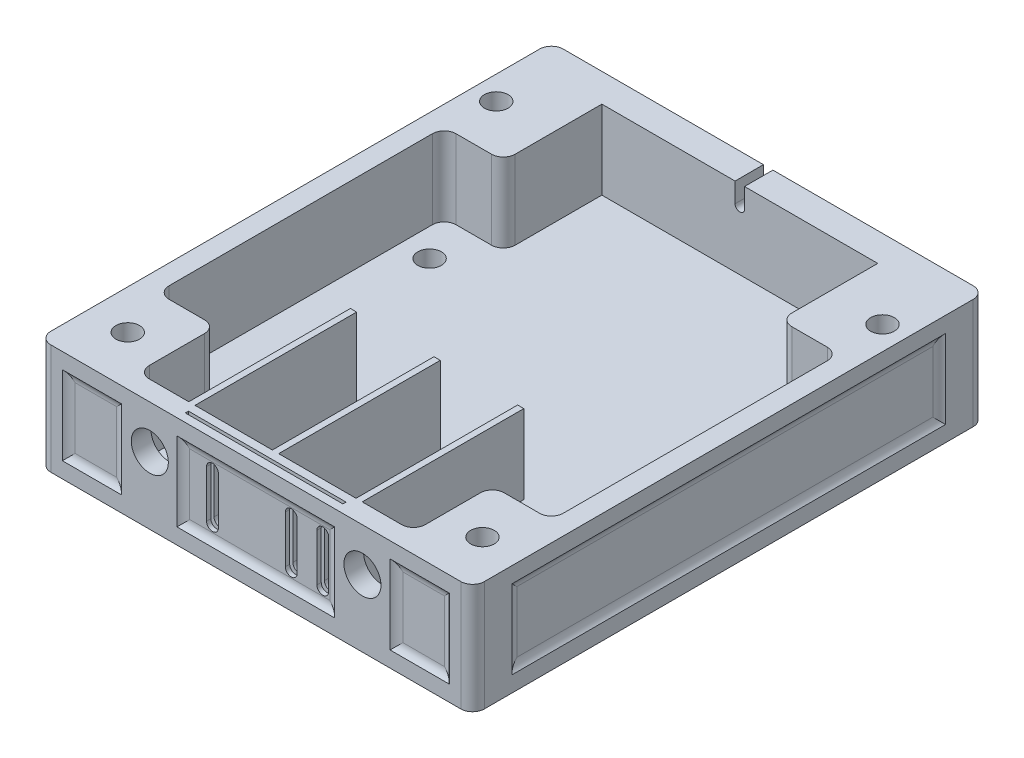
SolidWorks part; units mm, degrees
ref_plane "Front Plane" through (0, 0, 0) normal (0, 0, 1) x (1, 0, 0)
ref_plane "Top Plane" through (0, 0, 0) normal (0, 1, 0) x (1, 0, 0)
ref_plane "Right Plane" through (0, 0, 0) normal (1, 0, 0) x (0, 0, -1)
sketch "Sketch1" plane through (0, 0, 0) normal (0, 1, 0) x (1, 0, 0)
  line L1 (0, 0) -> (139.7, 0)
  line L2 (0, 0) -> (0, 165.1)
  line L3 (0, 165.1) -> (139.7, 165.1)
  line L4 (139.7, 0) -> (139.7, 165.1)
  dimension "D1" = 139.7
  dimension "D2" = 165.1
extrude "Boss-Extrude1" add sketch "Sketch1" along normal blind 10.16
sketch "Sketch2" plane through (0, 10.16, 0) normal (0, 1, 0) x (1, 0, 0)
  line L0 (69.85, 165.1) -> (69.85, 0) construction
  line L1 (139.7, 165.1) -> (0, 165.1) construction
  line L2 (0, 0) -> (139.7, 0) construction
  line L3 (124.35, 110.49) -> (15.35, 110.49) construction
  circle A0 centre (15.35, 110.49) radius 3.81
  circle A1 centre (124.35, 110.49) radius 3.81
  point P9 (69.85, 110.49)
  dimension "D3" = 7.62
  dimension "D4" = 7.62
  dimension "D1" = 109
  dimension "D2" = 54.61
extrude "Cut-Extrude1" cut sketch "Sketch2" against normal up to surface (10.16 mm away) up to face at (69.85, 0, -82.55)
sketch "Sketch3" plane through (0, 10.16, 0) normal (0, 1, 0) x (1, 0, 0)
  line L0 (6.35, 124.206) -> (25.4, 124.206)
  line L1 (25.4, 124.206) -> (25.4, 155.956)
  line L3 (133.35, 124.46) -> (114.3, 124.46)
  line L7 (6.35, 31.75) -> (25.4, 31.75)
  line L8 (6.35, 158.75) -> (6.35, 6.35)
  line L9 (6.35, 6.35) -> (133.35, 6.35)
  line L10 (133.35, 6.35) -> (133.35, 158.75)
  line L11 (133.35, 158.75) -> (6.35, 158.75)
  line L12 (6.35, 124.206) -> (6.35, 31.75)
  line L13 (25.4, 6.35) -> (114.3, 6.35)
  line L14 (133.35, 31.75) -> (133.35, 124.46)
  line L16 (25.4, 6.35) -> (25.4, 31.75)
  line L17 (133.35, 31.75) -> (114.3, 31.75)
  line L18 (114.3, 6.35) -> (114.3, 31.75)
  line L19 (114.3, 124.46) -> (114.3, 155.956)
  line L20 (25.4, 155.956) -> (69.85, 155.956)
  line L21 (69.85, 155.956) -> (114.3, 155.956)
  line L23 (0, 165.1) -> (0, 0)
  line L24 (0, 0) -> (139.7, 0)
  line L25 (139.7, 0) -> (139.7, 165.1)
  line L26 (139.7, 165.1) -> (0, 165.1)
  line L27 (0, 165.1) -> (0, 0)
  line L28 (0, 0) -> (139.7, 0)
  line L29 (139.7, 0) -> (139.7, 165.1)
  line L30 (139.7, 165.1) -> (0, 165.1)
  dimension "D2" = 25.4
  dimension "D3" = 19.05
  dimension "D5" = 31.75
  dimension "D6" = 19.05
  dimension "D7" = 92.71
  dimension "D8" = 9.144
  dimension "D1" = 6.35
  dimension "D4" = 0
extrude "Boss-Extrude2" add sketch "Sketch3" along normal blind 25.4
sketch "Sketch5" plane through (0, 0, 0) normal (0, 0, 1) x (1, 0, 0)
  line L0 (69.85, 35.56) -> (69.85, 0) construction
  line L1 (0, 35.56) -> (139.7, 35.56) construction
  line L2 (0, 0) -> (139.7, 0) construction
  line L4 (49.53, 10.16) -> (90.17, 10.16) construction
  line L5 (49.53, 10.16) -> (49.53, 25.4) construction
  line L6 (49.53, 25.4) -> (90.17, 25.4) construction
  line L7 (90.17, 10.16) -> (90.17, 25.4) construction
  line L8 (69.85, 25.4) -> (69.85, 10.16) construction
  line L9 (49.53, 17.78) -> (90.17, 17.78) construction
  line L10 (51.435, 25.4) -> (51.435, 10.16) construction
  line L11 (57.785, 25.4) -> (57.785, 10.16) construction
  line L12 (61.595, 25.4) -> (61.595, 10.16) construction
  line L13 (78.105, 25.4) -> (78.105, 10.16)
  line L14 (81.915, 25.4) -> (81.915, 10.16)
  line L15 (88.265, 25.4) -> (88.265, 10.16)
  line L17 (47.625, 25.4) -> (47.625, 10.16) construction
  line L18 (92.075, 25.4) -> (92.075, 10.16)
  line L19 (59.69, 27.305) -> (59.69, 8.255) construction
  line L20 (49.53, 13.9505) -> (54.61, 13.9505) construction
  line L21 (54.61, 13.9505) -> (54.61, 30.0028) construction
  line L22 (52.07, 13.9505) -> (52.07, 30.0028) construction
  line L23 (56.515, 25.4) -> (56.515, 10.16)
  line L24 (52.705, 25.4) -> (52.705, 10.16)
  circle A0 centre (104.21, 21.66) radius 4.25 construction
  circle A1 centre (35.69, 21.66) radius 4.25 construction
  circle A2 centre (104.21, 21.66) radius 4.25 construction
  circle A3 centre (35.69, 21.66) radius 4.25 construction
  arc A4 (51.435, 25.4) -> (47.625, 25.4) centre (49.53, 25.4) ccw construction
  arc A6 (61.595, 25.4) -> (57.785, 25.4) centre (59.69, 25.4) ccw construction
  arc A7 (57.785, 10.16) -> (61.595, 10.16) centre (59.69, 10.16) ccw construction
  arc A8 (78.105, 25.4) -> (81.915, 25.4) centre (80.01, 25.4) cw
  arc A9 (81.915, 10.16) -> (78.105, 10.16) centre (80.01, 10.16) cw
  arc A11 (88.265, 25.4) -> (92.075, 25.4) centre (90.17, 25.4) cw
  circle A12 centre (35.69, 21.66) radius 5.969
  circle A13 centre (104.21, 21.66) radius 5.969
  arc A14 (51.435, 10.16) -> (47.625, 10.16) centre (49.53, 10.16) cw construction
  arc A15 (88.265, 10.16) -> (92.075, 10.16) centre (90.17, 10.16) ccw
  arc A16 (52.705, 10.16) -> (56.515, 10.16) centre (54.61, 10.16) ccw
  arc A17 (52.705, 25.4) -> (56.515, 25.4) centre (54.61, 25.4) cw
  point P12 (69.85, 17.78)
  dimension "D3" = 3.81
  dimension "D5" = 3.81
  dimension "D6" = 3.81
  dimension "D9" = 11.938
  dimension "D10" = 11.938
  dimension "D1" = 40.64
  dimension "D2" = 15.24
  dimension "D7" = 10.16
  dimension "D8" = 10.16
extrude "Cut-Extrude3" cut sketch "Sketch5" against normal up to surface (6.35 mm away) up to face at (69.85, 22.86, -6.35)
fillet "Fillet1" radius 3.81 14 edges at (133.35, 22.86, -31.75) (114.3, 22.86, -31.75) (114.3, 22.86, -6.35) (6.35, 22.86, -31.75) (25.4, 22.86, -6.35) (25.4, 22.86, -31.75) (139.7, 17.78, -165.1) (139.7, 17.78, 0) (0, 17.78, 0) (0, 17.78, -165.1) (133.35, 22.86, -124.46) (114.3, 22.86, -124.46) (25.4, 22.86, -124.206) (6.35, 22.86, -124.206)
sketch "Sketch6" plane through (0, 35.56, 0) normal (0, 1, 0) x (1, 0, 0)
  line L0 (25.4, 10.16) -> (25.4, 0) construction
  line L1 (3.81, 0) -> (135.89, 0) construction
  line L2 (25.4, 0) -> (0, 0) construction
  line L3 (10.16, 31.75) -> (0, 31.75) construction
  line L4 (0, 161.29) -> (0, 3.81) construction
  line L5 (0, 31.75) -> (0, 0) construction
  line L6 (0, 15.875) -> (12.7, 15.875) construction
  line L7 (69.85, 0) -> (69.85, 22.805) construction
  line L8 (12.7, 15.875) -> (12.7, 0) construction
  circle A0 centre (12.7, 15.875) radius 3.81
  circle A1 centre (127, 15.875) radius 3.81
  dimension "D1" = 7.62
extrude "Cut-Extrude4" cut sketch "Sketch6" against normal blind 25.4
sketch "Sketch7" plane through (0, 10.16, 0) normal (0, 1, 0) x (1, 0, 0)
  line L0 (69.85, 6.35) -> (69.85, 39.688) construction
  line L1 (29.21, 6.35) -> (110.49, 6.35) construction
  line L2 (116.85, 44.45) -> (22.85, 44.45) construction
  line L3 (29.21, 6.35) -> (52.705, 6.35) construction
  circle A0 centre (22.85, 44.45) radius 3.175
  circle A1 centre (116.85, 44.45) radius 3.175
  point P7 (69.85, 44.45)
  dimension "D3" = 6.35
  dimension "D4" = 6.35
  dimension "D1" = 94
  dimension "D2" = 38.1
extrude "Cut-Extrude5" cut sketch "Sketch7" against normal up to surface (10.16 mm away) up to face at (15.35, 0, -114.3)
sketch "Sketch12" plane through (0, 0, -165.1) normal (0, 0, -1) x (-1, 0, 0)
  line L0 (-71.755, 17.78) -> (-67.945, 17.78) construction
  line L2 (-111.125, 27.305) -> (-28.575, 27.305)
  line L3 (-111.125, 27.305) -> (-111.125, 8.255)
  line L4 (-111.125, 8.255) -> (-28.575, 8.255)
  line L5 (-28.575, 27.305) -> (-28.575, 8.255)
  line L6 (-69.85, 8.255) -> (-69.85, 27.305) construction
  line L7 (-111.125, 17.78) -> (-28.575, 17.78) construction
  point P4 (-69.85, 17.78)
  dimension "D1" = 82.55
  dimension "D2" = 19.05
extrude "Cut-Extrude9" cut sketch "Sketch12" against normal blind 1.27
sketch "Sketch13" plane through (0, 0, 0) normal (0, 0, 1) x (1, 0, 0)
  line L0 (69.85, 35.56) -> (69.85, 0) construction
  line L1 (3.81, 35.56) -> (135.89, 35.56) construction
  line L2 (3.81, 0) -> (135.89, 0) construction
  line L3 (3.81, 17.78) -> (30.2788, 17.78) construction
  line L4 (44.45, 5.08) -> (95.25, 5.08)
  line L5 (44.45, 5.08) -> (44.45, 30.48)
  line L6 (44.45, 30.48) -> (95.25, 30.48)
  line L7 (95.25, 5.08) -> (95.25, 30.48)
  line L8 (69.85, 30.48) -> (69.85, 5.08) construction
  line L9 (44.45, 17.78) -> (95.25, 17.78) construction
  line L10 (3.81, 35.56) -> (3.81, 0) construction
  line L11 (132.1806, 5.08) -> (113.1306, 5.08)
  line L12 (7.5194, 5.08) -> (26.5694, 5.08)
  line L13 (7.5194, 5.08) -> (7.5194, 30.48)
  line L14 (7.5194, 30.48) -> (26.5694, 30.48)
  line L15 (26.5694, 5.08) -> (26.5694, 30.48)
  line L16 (17.0444, 30.48) -> (17.0444, 5.08) construction
  line L17 (7.5194, 17.78) -> (26.5694, 17.78) construction
  line L18 (113.1306, 5.08) -> (113.1306, 30.48)
  line L19 (132.1806, 30.48) -> (113.1306, 30.48)
  line L20 (132.1806, 5.08) -> (132.1806, 30.48)
  point P6 (69.85, 17.78)
  point P14 (17.0444, 17.78)
  dimension "D1" = 50.8
  dimension "D2" = 25.4
  dimension "D3" = 26.4688
  dimension "D4" = 25.4
  dimension "D5" = 19.05
extrude "Cut-Extrude10" cut sketch "Sketch13" against normal blind 1.27
fillet "Fillet3" radius 3.81 12 edges at (69.85, 5.08, -1.27) (44.45, 17.78, -1.27) (95.25, 17.78, -1.27) (69.85, 30.48, -1.27) (132.1806, 17.78, -1.27) (122.6556, 30.48, -1.27) (122.6556, 5.08, -1.27) (113.1306, 17.78, -1.27) (17.0444, 5.08, -1.27) (7.5194, 17.78, -1.27) (17.0444, 30.48, -1.27) (26.5694, 17.78, -1.27)
fillet "Fillet4" radius 3.81 3 edges at (28.575, 17.78, -163.83) (69.85, 8.255, -163.83) (111.125, 17.78, -163.83)
sketch "Sketch17" plane through (0, 0, 0) normal (-1, 0, 0) x (0, 0, 1)
  line L0 (-82.55, 35.56) -> (-82.55, 0) construction
  line L1 (-161.29, 35.56) -> (-3.81, 35.56) construction
  line L2 (-161.29, 0) -> (-3.81, 0) construction
  line L4 (-12.7, 5.08) -> (-152.4, 5.08)
  line L5 (-12.7, 5.08) -> (-12.7, 30.48)
  line L6 (-12.7, 30.48) -> (-152.4, 30.48)
  line L7 (-152.4, 5.08) -> (-152.4, 30.48)
  line L8 (-82.55, 30.48) -> (-82.55, 5.08) construction
  line L9 (-12.7, 17.78) -> (-152.4, 17.78) construction
  point P6 (-82.55, 17.78)
  dimension "D1" = 139.7
  dimension "D2" = 25.4
extrude "Cut-Extrude11" cut sketch "Sketch17" against normal blind 1.27
sketch "Sketch18" plane through (139.7, 0, 0) normal (1, 0, 0) x (0, 0, -1)
  line L0 (82.55, 35.56) -> (82.55, 0) construction
  line L1 (3.81, 35.56) -> (161.29, 35.56) construction
  line L2 (3.81, 0) -> (161.29, 0) construction
  line L4 (152.4, 5.08) -> (12.7, 5.08)
  line L5 (152.4, 5.08) -> (152.4, 30.48)
  line L6 (152.4, 30.48) -> (12.7, 30.48)
  line L7 (12.7, 5.08) -> (12.7, 30.48)
  line L8 (82.55, 30.48) -> (82.55, 5.08) construction
  line L9 (152.4, 17.78) -> (12.7, 17.78) construction
  point P6 (82.55, 17.78)
  dimension "D1" = 139.7
  dimension "D2" = 25.4
extrude "Cut-Extrude12" cut sketch "Sketch18" against normal blind 1.27
fillet "Fillet5" radius 3.81 8 edges at (1.27, 17.78, -12.7) (1.27, 5.08, -82.55) (1.27, 30.48, -82.55) (1.27, 17.78, -152.4) (138.43, 17.78, -152.4) (138.43, 5.08, -82.55) (138.43, 30.48, -82.55) (138.43, 17.78, -12.7)
sketch "Sketch19" plane through (0, 35.56, 0) normal (0, 1, 0) x (1, 0, 0)
  line L0 (0, 161.29) -> (0, 3.81) construction
  line L2 (135.89, 165.1) -> (3.81, 165.1) construction
  line L3 (139.7, 3.81) -> (139.7, 161.29) construction
  line L4 (135.89, 165.1) -> (3.81, 165.1) construction
  circle A0 centre (7.62, 139.7) radius 3.81
  circle A2 centre (132.08, 139.7) radius 3.81
  dimension "D1" = 7.62
  dimension "D4" = 7.62
  dimension "D2" = 7.62
  dimension "D3" = 25.4
  dimension "D5" = 7.62
  dimension "D6" = 25.4
extrude "Cut-Extrude13" cut sketch "Sketch19" against normal blind 25.4
sketch "Sketch20" plane through (0, 0, -165.1) normal (0, 0, -1) x (-1, 0, 0)
  line L0 (-69.85, 35.56) -> (-69.85, 29.21) construction
  line L6 (-135.89, 35.56) -> (-3.81, 35.56) construction
  line L7 (-71.374, 29.21) -> (-71.374, 35.56)
  line L8 (-71.374, 35.56) -> (-68.326, 35.56)
  line L9 (-68.326, 35.56) -> (-68.326, 29.21)
  arc A1 (-71.374, 29.21) -> (-68.326, 29.21) centre (-69.85, 29.21) ccw
  dimension "D1" = 3.048
  dimension "D2" = 6.35
extrude "Cut-Extrude14" cut sketch "Sketch20" against normal up to surface (9.144 mm away) up to face at (69.85, 22.86, -155.956)
chamfer "Chamfer1" distance 2.54 angle 45 3 edges at (90.17, 10.16, -6.35) (80.01, 10.16, -6.35) (54.61, 10.16, -6.35)
sketch "Sketch21" plane through (0, 10.16, 0) normal (0, 1, 0) x (1, 0, 0)
  line L0 (41.91, 6.35) -> (41.91, 58.42)
  line L1 (29.21, 6.35) -> (110.49, 6.35) construction
  line L2 (41.91, 58.42) -> (43.91, 58.42)
  line L3 (43.91, 58.42) -> (43.91, 6.35)
  line L4 (29.21, 6.35) -> (52.705, 6.35) construction
  line L5 (43.91, 6.35) -> (41.91, 6.35)
  line L6 (25.4, 27.94) -> (25.4, 10.16) construction
  line L7 (97.79, 6.35) -> (97.79, 58.42)
  line L8 (92.075, 6.35) -> (110.49, 6.35) construction
  line L9 (97.79, 58.42) -> (95.79, 58.42)
  line L10 (95.79, 58.42) -> (95.79, 6.35)
  line L11 (95.79, 6.35) -> (97.79, 6.35)
  line L12 (114.3, 10.16) -> (114.3, 27.94) construction
  line L20 (43.91, 6.35) -> (95.79, 6.35) construction
  line L21 (69.85, 6.35) -> (69.85, 58.42) construction
  line L22 (69.85, 58.42) -> (43.91, 58.42) construction
  line L24 (70.866, 6.35) -> (68.834, 6.35)
  line L25 (70.866, 6.35) -> (70.866, 58.42)
  line L26 (70.866, 58.42) -> (68.834, 58.42)
  line L27 (68.834, 6.35) -> (68.834, 58.42)
  line L28 (69.85, 58.42) -> (69.85, 6.35) construction
  line L29 (70.866, 32.385) -> (68.834, 32.385) construction
  point P20 (69.85, 32.385)
  dimension "D1" = 2
  dimension "D2" = 52.07
  dimension "D3" = 16.51
  dimension "D4" = 2
  dimension "D5" = 52.07
  dimension "D6" = 16.51
  dimension "D7" = 2.032
extrude "Boss-Extrude3" add sketch "Sketch21" along normal up to surface (25.4 mm away) up to face at (69.85, 35.56, -85.1332)
sketch "Sketch22" plane through (0, 35.56, 0) normal (0, 1, 0) x (1, 0, 0)
  line L0 (69.85, 0) -> (69.85, 6.35) construction
  line L1 (3.81, 0) -> (135.89, 0) construction
  line L2 (95.25, 2.667) -> (44.45, 2.667)
  line L3 (44.45, 2.667) -> (44.45, 3.683)
  line L4 (44.45, 3.175) -> (69.85, 3.175) construction
  line L5 (95.25, 3.683) -> (44.45, 3.683)
  line L6 (95.25, 2.667) -> (95.25, 3.683)
  point P11 (69.85, 2.667)
  point P12 (69.85, 3.683)
  dimension "D1" = 6.35
  dimension "D2" = 0.508
  dimension "D3" = 50.8
extrude "Cut-Extrude15" cut sketch "Sketch22" against normal blind 29.21
